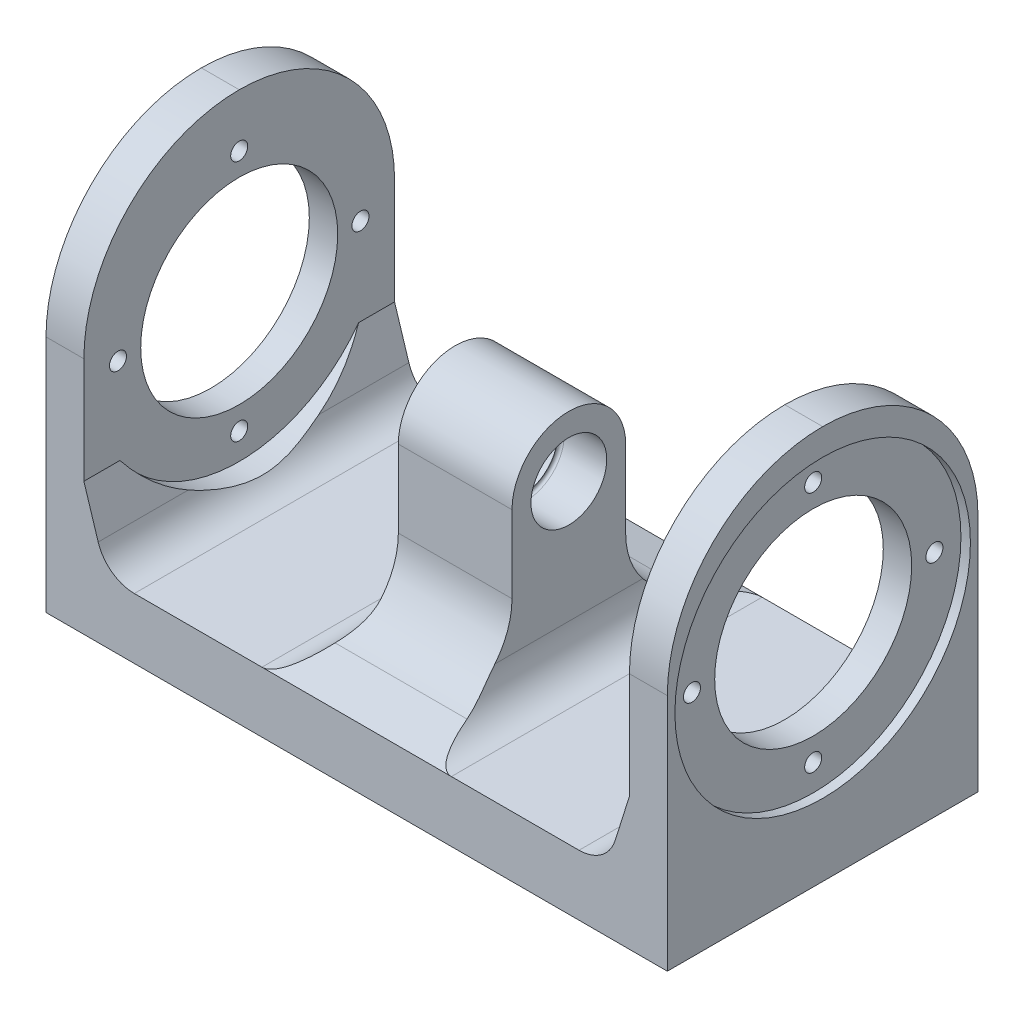
SolidWorks part; units mm, degrees
material "6061 Alloy"
ref_plane "Front Plane" through (0, 0, 0) normal (0, 0, 1) x (1, 0, 0)
ref_plane "Top Plane" through (0, 0, 0) normal (0, 1, 0) x (1, 0, 0)
ref_plane "Right Plane" through (0, 0, 0) normal (1, 0, 0) x (0, 0, -1)
sketch "Sketch1" plane through (0, 0, 0) normal (0, 0, 1) x (1, 0, 0)
  line L0 (0, 0) -> (-72, 0)
  line L1 (55, 0) -> (-55, 0) construction
  line L3 (-82, 0) -> (-82, 104)
  line L4 (-82, 104) -> (-72, 104)
  line L5 (-72, 104) -> (-72, 10)
  line L7 (-72, 10) -> (-15, 10)
  line L9 (-15, 10) -> (-15, 74)
  line L10 (-15, 74) -> (0, 74)
  line L11 (0, -55) -> (0, 55) construction
  line L12 (0, 74) -> (0, 0)
  line L13 (-82, 0) -> (-72, 0)
  dimension "D1" = 15
  dimension "D2" = 64
  dimension "D4" = 82
  dimension "D5" = 10
  dimension "D6" = 10
  dimension "D8" = 30
extrude "Boss-Extrude1" add sketch "Sketch1" against normal blind 82
sketch "Sketch5" plane through (-15, 0, 0) normal (-1, 0, 0) x (0, 0, 1)
  line L0 (-82, 74) -> (0, 74) construction
  line L1 (0, 74) -> (0, 10) construction
  circle A0 centre (-41, 58) radius 10
  dimension "D3" = 20
  dimension "D1" = 16
  dimension "D2" = 41
extrude "Cut-Extrude1" cut sketch "Sketch5" against normal blind 12
sketch "Sketch6" plane through (-3, 0, 0) normal (-1, 0, 0) x (0, 0, 1)
  circle A0 centre (-41, 58) radius 9
  dimension "D1" = 18
extrude "Cut-Extrude2" cut sketch "Sketch6" against normal up to next
sketch "Sketch8" plane through (-72, 0, 0) normal (1, 0, 0) x (0, 0, -1)
  circle A0 centre (41, 58) radius 26
  circle A1 centre (41, 58) radius 9 construction
  dimension "D1" = 52
extrude "Cut-Extrude4" cut sketch "Sketch8" against normal up to next
sketch "Sketch10" plane through (0, 0, 0) normal (1, 0, 0) x (0, 0, -1)
  line L1 (0, 55) -> (0, -55) construction
  line L2 (82, 0) -> (82, 74) construction
  line L5 (0, 10) -> (0, 74)
  line L6 (82, 74) -> (0, 74) construction
  line L7 (0, 74) -> (82, 74)
  line L8 (82, 74) -> (82, 10)
  line L9 (26, 59) -> (26, 38.6588)
  line L11 (26, 10) -> (56, 10)
  line L13 (82, 0) -> (0, 0) construction
  line L14 (26, 10) -> (0, 10)
  line L15 (0, 74) -> (82, 74)
  line L16 (82, 10) -> (56, 10)
  line L17 (56, 59) -> (56, 38.6588)
  line L18 (11.7143, 19.4925) -> (0, 16)
  line L19 (0, 16) -> (0, 10)
  line L20 (70.2857, 19.4925) -> (82, 16)
  line L21 (82, 16) -> (82, 10)
  arc A0 (26, 59) -> (56, 59) centre (41, 59) cw
  arc A1 (56, 38.6588) -> (70.2857, 19.4925) centre (76, 38.6588) ccw
  arc A2 (26, 38.6588) -> (11.7143, 19.4925) centre (6, 38.6588) cw
  point P18 (41, 74)
  point P23 (56, 29)
  dimension "D2" = 15
  dimension "D4" = 20
  dimension "D5" = 6
  dimension "D1" = 10
  dimension "D3" = 30
extrude "Cut-Extrude5" cut sketch "Sketch10" against normal up to next
fillet "Fillet3" radius 41 2 edges at (-77, 104, -82) (-77, 104, 0)
sketch "Sketch13" plane through (-82, 0, 0) normal (-1, 0, 0) x (0, 0, 1)
  circle A0 centre (-41, 58) radius 39
  dimension "D1" = 78
extrude "Cut-Extrude6" cut sketch "Sketch13" against normal blind 2.5
hole_wizard "M4 Clearance Hole1" positions "Sketch14" profile "Sketch15" hole size "M4" standard "ANSI Metric" end condition up to next
sketch "Sketch14" plane through (-79.5, 0, 0) normal (-1, 0, 0) x (0, 0, 1)
  circle A0 centre (-41, 58) radius 32
  point P0 (-41, 90)
  point P2 (-9, 58)
  point P4 (-41, 26)
  point P6 (-73, 58)
  dimension "D1" = 64
sketch "Sketch15" plane through (-79.5, 90, -41) normal (0, 1, 0) x (0, 0, 1)
  line L0 (0, 0) -> (0, 7.5)
  line L1 (0, 7.5) -> (2.25, 7.5)
  line L2 (2.25, 7.5) -> (2.25, 0)
  line L5 (2.25, 0) -> (0, 0)
  line L11 (0, -6.35) -> (0, 107.95) construction
  dimension "Thru Hole Dia." = 4.5
  dimension "Thru Hole Depth" = 7.5
fillet "Fillet5" radius 0.8 1 edges at (-3, 48, -41)
mirror "Mirror1" about plane through (0, 74, -82) normal (1, 0, 0) of bodies 118 119
chamfer "Chamfer2" distance 5 angle 45 2 edges at (-72, 10, -41) (72, 10, -41)
sketch "Sketch18" plane through (0, 0, 0) normal (0, 0, 1) x (1, 0, 0)
  line L0 (-72, 35) -> (-68.2262, 23)
  line L1 (-72, 15) -> (-72, 63) construction
  line L2 (-58.6868, 16) -> (0, 16)
  line L6 (-67, 10) -> (-72, 15)
  line L7 (-72, 15) -> (-72, 35)
  line L8 (0, -55) -> (0, 55) construction
  line L9 (0, 16) -> (0, 10)
  line L11 (0, 10) -> (-67, 10)
  arc A0 (-68.2262, 23) -> (-58.6868, 16) centre (-58.6868, 26) ccw
  dimension "D1" = 10
  dimension "D2" = 20
  dimension "D3" = 6
  dimension "D4" = 12
extrude "Boss-Extrude3" add sketch "Sketch18" against normal up to surface (82 mm away) up to face at (0, 25.2857, -82)
mirror "Mirror2" about plane through (0, 0, 0) normal (1, 0, 0) of "Boss-Extrude3"
sketch "Sketch19" plane through (-72, 0, 0) normal (1, 0, 0) x (0, 0, -1)
  circle A0 centre (41, 58) radius 39
  dimension "D1" = 78
extrude "Cut-Extrude7" cut sketch "Sketch19" along normal blind 20
mirror "Mirror3" about plane through (0, 0, 0) normal (1, 0, 0) of "Cut-Extrude7"
fillet "Fillet6" radius 10 2 edges at (-15, 16, -41) (15, 16, -41)
